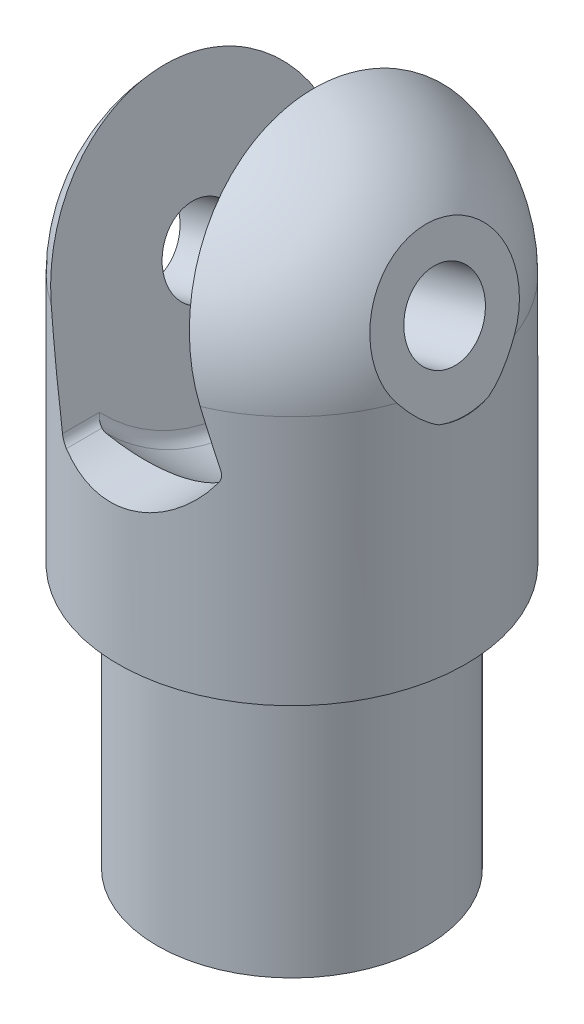
SolidWorks part; units mm, degrees
ref_plane "Front Plane" through (0, 0, 0) normal (0, 0, 1) x (1, 0, 0)
ref_plane "Top Plane" through (0, 0, 0) normal (0, 1, 0) x (1, 0, 0)
ref_plane "Right Plane" through (0, 0, 0) normal (1, 0, 0) x (0, 0, -1)
sketch "Sketch1" plane through (0, 0, 0) normal (0, 1, 0) x (1, 0, 0)
  circle A0 centre (0, 0) radius 12.9921
extrude "Boss-Extrude1" add sketch "Sketch1" along normal blind 25.4 contours A0
sketch "Sketch2" plane through (0, 0, 0) normal (1, 0, 0) x (0, 0, -1)
  line L0 (-16.764, 25.4) -> (-16.764, 49.53)
  line L1 (0, 25.4) -> (-16.764, 25.4)
  line L4 (12.9921, 25.4) -> (-12.9921, 25.4) construction
  line L5 (0, 14.2913) -> (0, -14.2913) construction
  line L6 (0, 25.4) -> (0, 66.294)
  arc A0 (0, 66.294) -> (-16.764, 49.53) centre (0, 49.53) ccw
  dimension "D1" = 33.528
  dimension "D2" = 24.13
revolve "Revolve1" add sketch "Sketch2" angle 360 about L6
ref_plane "Plane2" through (0, 49.53, 0) normal (0, -1, 0) x (-1, 0, 0)
ref_axis "Axis1" through (0, 49.53, 23.7) along (0, 0, -1)
ref_plane "Plane3" through (-12.3825, 46.2121, 0) normal (0.2588, -0.9659, 0) x (0, 0, -1)
ref_plane "Plane4" through (12.3825, 3.3179, 0) normal (-0.9659, -0.2588, 0) x (0, 0, -1)
sketch "Sketch3" plane through (-13.0614, 98.2757, 0) normal (-0.9659, -0.2588, 0) x (0, 0, -1)
  line L1 (-23.7, 50.4652) -> (13.1808, 50.4652) construction
  line L2 (0, 50.4652) -> (0, 73.773) construction
  circle A2 centre (0, 50.4652) radius 3.81
  dimension "D1" = 7.62
extrude "Cut-Extrude1" cut sketch "Sketch3" against normal through all both and the other way through all
ref_axis "Axis2" through (17.6091, 54.2484, 0) along (-0.9659, -0.2588, 0)
sketch "Sketch10" plane through (0, 0, 0) normal (0, 0, 1) x (1, 0, 0)
  line L0 (17.6091, 54.2484) -> (-17.8154, 44.7564) construction
  line L1 (-8.5871, 47.2291) -> (6.1336, 51.1735)
  point P5 (-1.2267, 49.2013)
  dimension "D1" = 15.24
  dimension "D2" = 1.27
sketch "Sketch11" plane through (0, 0, 0) normal (0, 0, 1) x (1, 0, 0)
  line L2 (-8.5871, 47.2291) -> (6.1336, 51.1735) construction
  line L3 (-8.5871, 47.2291) -> (-12.7611, 62.8066)
  line L4 (6.1336, 51.1735) -> (1.6598, 67.87)
  line L5 (-8.5871, 47.2291) -> (6.1336, 51.1735)
  arc A0 (1.6598, 67.87) -> (-12.7611, 62.8066) centre (0, 49.53) ccw
  arc A1 (14.7829, 57.4355) -> (-16.764, 49.53) centre (0, 49.53) ccw construction
  dimension "D1" = 18.415
revolve "Cut-Revolve10" cut sketch "Sketch11" angle 180 about axis through (17.6091, 54.2484, 0) along (-0.9659, -0.2588, 0) other way angle 90
sketch "Sketch13" plane through (0, 0, 0) normal (0, 0, 1) x (1, 0, 0)
  line L0 (-9.5732, 50.9093) -> (5.1475, 54.8537)
  line L1 (-9.2036, 49.53) -> (-12.2656, 60.9575) construction
  line L2 (2.1181, 66.1597) -> (6.574, 49.53) construction
  line L3 (-8.5871, 47.2291) -> (6.1336, 51.1735) construction
  line L4 (-9.5732, 50.9093) -> (-13.9121, 67.1025)
  line L5 (5.1475, 54.8537) -> (0.8086, 71.0469)
  arc A0 (0.8086, 71.0469) -> (-13.9121, 67.1025) centre (-2.2128, 52.8815) ccw
  dimension "D1" = 3.81
  dimension "D2" = 36.83
revolve "Cut-Revolve11" cut sketch "Sketch13" angle 360 about L0
sketch "Sketch14" plane through (0, 0, 0) normal (0, 0, 1) x (1, 0, 0)
  line L0 (-8.5871, 47.2291) -> (6.1336, 51.1735) construction
  line L1 (-8.5871, 47.2291) -> (-6.6547, 40.0175)
  line L2 (6.1336, 51.1735) -> (8.066, 43.9619)
  line L3 (-8.5871, 47.2291) -> (6.1336, 51.1735)
  arc A0 (-6.6547, 40.0175) -> (8.066, 43.9619) centre (-1.2267, 49.2013) ccw
  dimension "D1" = 21.336
extrude "Cut-Extrude4" cut sketch "Sketch14" along normal blind 32.004
fillet "Fillet1" radius 1.27 8 edges at (-5.1686, 34.4711, -9.2535) (-4.8237, 33.1838, 0) (-5.6052, 36.1006, 6.7827) (-6.6547, 40.0175, 13.8961) (8.066, 43.9619, 13.5508) (9.1155, 40.045, 6.7827) (10.047, 36.5687, 0) (10.0783, 36.4517, -8.1547)
ref_plane "Plane5" through (-2.3382, -0.6265, 0) normal (-0.9659, -0.2588, 0) x (0, 0, -1)
sketch "Sketch15" plane through (-2.3382, -0.6265, 0) normal (-0.9659, -0.2588, 0) x (0, 0, -1)
  circle A0 centre (0, -47.8423) radius 7.62
  dimension "D1" = 15.24
extrude "Cut-Extrude5" cut sketch "Sketch15" along normal blind 10.16
mirror "Mirror1" about plane through (12.3825, 3.3179, 0) normal (-0.9659, -0.2588, 0) of "Cut-Extrude5"
